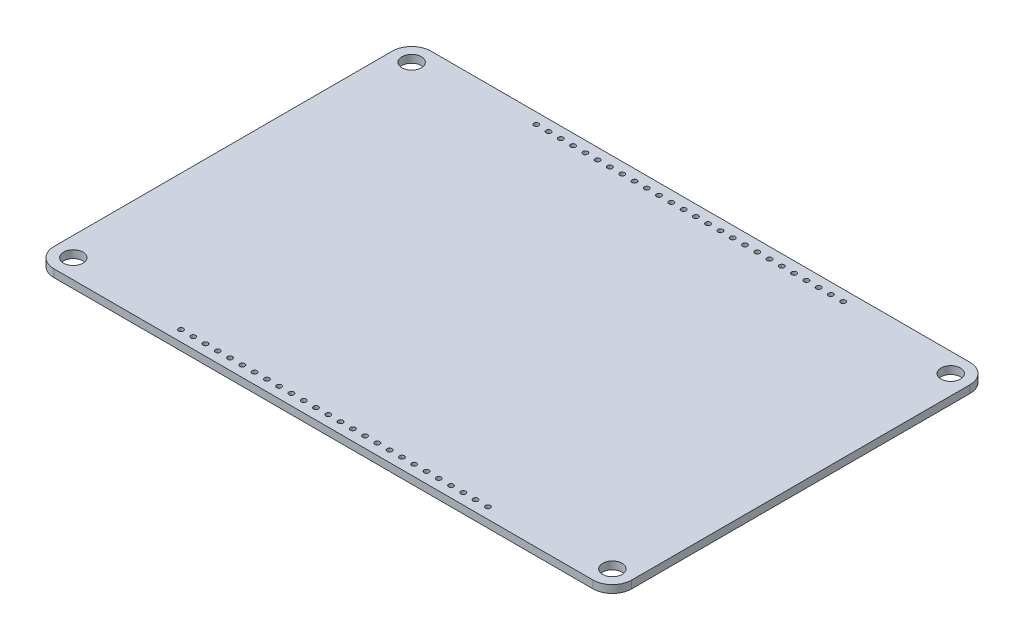
SolidWorks part; units mm, degrees
ref_plane "Front Plane" through (0, 0, 0) normal (0, 0, 1) x (1, 0, 0)
ref_plane "Top Plane" through (0, 0, 0) normal (0, 1, 0) x (1, 0, 0)
ref_plane "Right Plane" through (0, 0, 0) normal (1, 0, 0) x (0, 0, -1)
ref_axis "Axis X" through (-88.99, 0, 0) along (1, 0, 0)
ref_axis "Axis Y" through (0, 55, 0) along (0, -1, 0)
ref_axis "Axis Z" through (0, 0, -88.99) along (0, 0, 1)
sketch "Sketch1" plane through (0, 0, 0) normal (0, 1, 0) x (1, 0, 0)
  line L1 (-59.7662, -39.0017) -> (59.7662, -39.0017)
  line L2 (-59.7662, -39.0017) -> (-59.7662, 39.0017)
  line L3 (-59.7662, 39.0017) -> (59.7662, 39.0017)
  line L4 (59.7662, -39.0017) -> (59.7662, 39.0017)
  line L5 (-59.7662, -39.0017) -> (59.7662, 39.0017) construction
  line L6 (-59.7662, 39.0017) -> (59.7662, -39.0017) construction
  point P0 (0, 0)
  dimension "D1" = 119.5324
  dimension "D2" = 78.0034
extrude "Boss-Extrude1" add sketch "Sketch1" along normal blind 1.5875
sketch "Sketch2" plane through (0, 1.5875, 0) normal (0, 1, 0) x (1, 0, 0)
  line L0 (0, 0) -> (-86.9901, 0) construction
  line L1 (-0.8731, 0) -> (0.8731, 0) construction
  line L2 (0, 0) -> (0, 75.5139) construction
  line L3 (0, -0.8731) -> (0, 0.8731) construction
  circle A0 centre (-55.7657, 35.0012) radius 2
  circle A1 centre (-55.7657, -35.0012) radius 2
  circle A2 centre (55.7657, 35.0012) radius 2
  circle A3 centre (55.7657, -35.0012) radius 2
  dimension "D1" = 111.5314
  dimension "D2" = 70.0024
  dimension "D3" = 4
extrude "Cut-Extrude1" cut sketch "Sketch2" against normal up to next
sketch "Sketch3" plane through (0, 1.5875, 0) normal (0, 1, 0) x (1, 0, 0)
  line L0 (0, 0) -> (-104.3039, 0) construction
  line L1 (-0.8731, 0) -> (0.8731, 0) construction
  circle A0 centre (-31.7373, 36.758) radius 0.508
  circle A1 centre (-55.7657, 35.0012) radius 2 construction
  circle A2 centre (-31.7373, -36.758) radius 0.508
  dimension "D1" = 1.016
  dimension "D2" = 24.0284
  dimension "D3" = 72.5
extrude "Cut-Extrude2" cut sketch "Sketch3" against normal up to next
sketch "Sketch11" plane through (0, 1.5875, 0) normal (0, 1, 0) x (1, 0, 0)
  line L0 (-59.7662, 39.0017) -> (-59.7662, -39.0017) construction
  line L1 (59.7662, 39.0017) -> (-59.7662, 39.0017) construction
  line L2 (-59.7662, 35.0012) -> (-59.7662, 39.0017)
  line L3 (-59.7662, 39.0017) -> (-55.7657, 39.0017)
  line L4 (0, 0) -> (-80.7962, 0) construction
  line L5 (-0.8731, 0) -> (0.8731, 0) construction
  line L6 (-59.7662, -39.0017) -> (-55.7657, -39.0017)
  line L7 (-59.7662, -35.0012) -> (-59.7662, -39.0017)
  line L8 (0, 0) -> (0, 58.3461) construction
  line L9 (59.7662, -35.0012) -> (59.7662, -39.0017)
  line L10 (59.7662, -39.0017) -> (55.7657, -39.0017)
  line L11 (59.7662, 39.0017) -> (55.7657, 39.0017)
  line L12 (59.7662, 35.0012) -> (59.7662, 39.0017)
  arc A0 (-59.7662, 35.0012) -> (-55.7657, 39.0017) centre (-55.7657, 35.0012) cw
  circle A1 centre (-55.7657, 35.0012) radius 2 construction
  arc A2 (-59.7662, -35.0012) -> (-55.7657, -39.0017) centre (-55.7657, -35.0012) ccw
  arc A3 (59.7662, -35.0012) -> (55.7657, -39.0017) centre (55.7657, -35.0012) cw
  arc A4 (59.7662, 35.0012) -> (55.7657, 39.0017) centre (55.7657, 35.0012) ccw
extrude "Cut-Extrude4" cut sketch "Sketch11" against normal up to next
pattern_linear "LPattern1" count 26 spacing 2.54 along (1, 0, 0) of "Cut-Extrude2"
